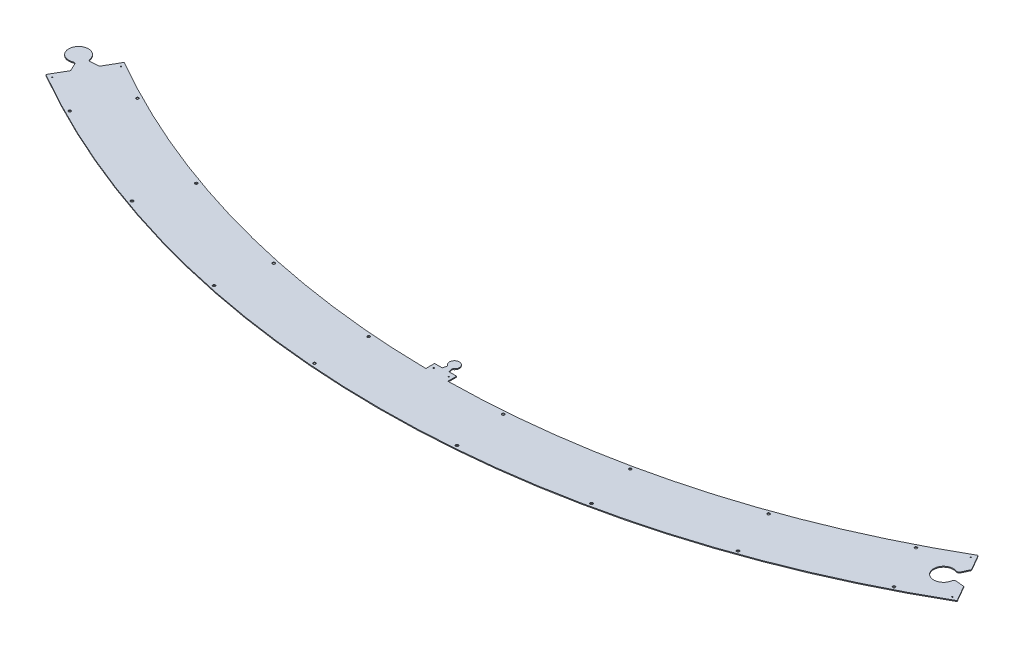
SolidWorks part; units mm, degrees
ref_plane "Front Plane" through (0, 0, 0) normal (0, 0, 1) x (1, 0, 0)
ref_plane "Top Plane" through (0, 0, 0) normal (0, 1, 0) x (1, 0, 0)
ref_plane "Right Plane" through (0, 0, 0) normal (1, 0, 0) x (0, 0, -1)
sketch "Sketch1" plane through (0, 0, 0) normal (0, 1, 0) x (1, 0, 0)
  line L0 (0, 0) -> (0, -2065) construction
  line L1 (0, 0) -> (-1032.5, -1788.3425) construction
  line L2 (0, 0) -> (1032.5, -1788.3425) construction
  line L3 (967.5, -1675.7592) -> (1032.5, -1788.3425)
  line L5 (-25, -1934.8385) -> (-25, -1915)
  line L6 (-25, -1915) -> (25, -1915)
  line L7 (25, -1934.8385) -> (25, -1915)
  line L8 (-967.5, -1675.7592) -> (-1032.5, -1788.3425)
  line L9 (0, 0) -> (933.8184, -1832.8208) construction
  line L10 (967.5, -1675.7592) -> (971.7433, -1673.3093) construction
  line L11 (1032.5, -1788.3425) -> (1036.3111, -1786.1421) construction
  arc A0 (-1032.5, -1788.3425) -> (1032.5, -1788.3425) centre (0, 0) ccw
  arc A1 (-967.5, -1675.7592) -> (-25, -1934.8385) centre (0, 0) ccw
  arc A2 (25, -1934.8385) -> (967.5, -1675.7592) centre (0, 0) ccw
  arc A3 (-967.5, -1675.7592) -> (967.5, -1675.7592) centre (0, 0) ccw construction
  circle A4 centre (-17, -1925) radius 1.25
  circle A5 centre (17, -1925) radius 1.25
  arc A7 (25.1034, -1942.8378) -> (971.5, -1682.6874) centre (0, 0) ccw construction
  circle A8 centre (962.8397, -1687.6874) radius 1.25
  arc A9 (-1028.5, -1781.4143) -> (1028.5, -1781.4143) centre (0, 0) ccw construction
  circle A10 centre (1019.8397, -1786.4143) radius 1.25
  circle A21 centre (686.5983, -1939.0286) radius 3
  circle A22 centre (933.8184, -1832.8208) radius 3
  circle A32 centre (427.6303, -2012.059) radius 3
  circle A33 centre (-1019.8397, -1786.4143) radius 1.25
  circle A34 centre (-962.8397, -1687.6874) radius 1.25
  circle A35 centre (161.3455, -2050.6625) radius 3
  circle A37 centre (-107.7, -2054.1786) radius 3 [skipped]
  circle A38 centre (882.0657, -1731.245) radius 3
  circle A39 centre (648.5467, -1831.5666) radius 3
  circle A40 centre (403.9308, -1900.5496) radius 3
  circle A41 centre (152.4036, -1937.0137) radius 3
  circle A43 centre (-101.7312, -1940.335) radius 3 [skipped]
  circle A44 centre (-152.4036, -1937.0137) radius 3
  circle A45 centre (-403.9308, -1900.5496) radius 3
  circle A46 centre (-648.5467, -1831.5666) radius 3
  circle A47 centre (-882.0657, -1731.245) radius 3
  circle A48 centre (-161.3455, -2050.6625) radius 3
  circle A49 centre (-427.6303, -2012.059) radius 3
  circle A50 centre (-933.8184, -1832.8208) radius 3
  circle A51 centre (-686.5983, -1939.0286) radius 3
  point P5 (0, -1915)
  point P41 (0, 0)
  point P50 (0, 0)
  point P53 (0, 0)
  point P71 (0, 0)
  dimension "D2" = 2065
  dimension "D4" = 2.5
  dimension "D9" = 8
  dimension "D10" = 6
  dimension "D12" = 8
  dimension "D13" = 10
  dimension "D14" = 5
  dimension "D15" = 5
  dimension "D16" = 107.7
  dimension "D19" = 2.5
  dimension "D1" = 30
  dimension "D3" = 50
  dimension "D5" = 150
  dimension "D7" = 10
  dimension "D8" = 8
  dimension "D11" = 10
  dimension "D17" = 8
  dimension "D18" = 8
  dimension "D6" = 130
extrude "Boss-Extrude2" add sketch "Sketch1" along normal blind 2
ref_axis "Axis1" through (0, 2.1, 0) along (0, -1, 0)
sketch "Sketch2" plane through (0, 2, 0) normal (0, 1, 0) x (1, 0, 0)
  line L0 (1000, -1732.0508) -> (965.359, -1752.0508) construction
  line L7 (992.8475, -1751.1632) -> (1012.0021, -1752.839)
  line L8 (1032.5, -1788.3425) -> (967.5, -1675.7592) construction
  line L10 (987.6795, -1750.7111) -> (977.6795, -1733.3906) construction
  line L11 (979.8719, -1728.6888) -> (987.9979, -1711.2626)
  line L13 (987.9979, -1711.2626) -> (1012.0021, -1752.839)
  arc A1 (973.5164, -1731.2312) -> (987.468, -1755.3961) centre (965.359, -1752.0508) ccw
  arc A2 (973.5164, -1731.2312) -> (979.8719, -1728.6888) centre (975.3404, -1726.5758) ccw
  arc A3 (992.8475, -1751.1632) -> (987.468, -1755.3961) centre (992.4117, -1756.1442) ccw
  point P9 (982.6795, -1742.0508)
  dimension "D4" = 20
  dimension "D5" = 5
  dimension "D1" = 10
  dimension "D2" = 40
  dimension "D3" = 35
sketch "Sketch4" plane through (0, 2, 0) normal (0, 1, 0) x (1, 0, 0)
  line L0 (-1000, -1732.0508) -> (-1034.641, -1712.0508) construction
  line L1 (-967.5, -1675.7592) -> (-1032.5, -1788.3425) construction
  line L2 (-1022.3205, -1730.7111) -> (-1012.3205, -1713.3906) construction
  line L3 (-1007.1525, -1712.9384) -> (-987.9979, -1711.2626)
  line L4 (-1020.1281, -1735.4128) -> (-1012.0021, -1752.839)
  line L5 (-987.9979, -1711.2626) -> (-1012.0021, -1752.839)
  line L6 (0, -1915) -> (0, -1895) construction
  line L7 (25, -1915) -> (-25, -1915) construction
  line L8 (0, -1905) -> (5, -1905) construction
  line L9 (5.4863, -1906.815) -> (7.6795, -1915)
  line L10 (-5.4863, -1906.815) -> (-7.6795, -1915)
  line L11 (-7.6795, -1915) -> (7.6795, -1915)
  arc A0 (-1012.532, -1708.7055) -> (-1026.4836, -1732.8704) centre (-1034.641, -1712.0508) ccw
  arc A1 (-1020.1281, -1735.4128) -> (-1026.4836, -1732.8704) centre (-1024.6596, -1737.5259) ccw
  arc A2 (-1007.1525, -1712.9384) -> (-1012.532, -1708.7055) centre (-1007.5883, -1707.9574) cw
  arc A3 (6.4573, -1904.1271) -> (-6.4573, -1904.1271) centre (0, -1895) ccw
  arc A4 (6.4573, -1904.1271) -> (5.4863, -1906.815) centre (7.9011, -1906.168) ccw
  arc A5 (-5.4863, -1906.815) -> (-6.4573, -1904.1271) centre (-7.9011, -1906.168) ccw
  point P7 (-1017.3205, -1722.0508)
  point P30 (-5, -1905)
  dimension "D5" = 5
  dimension "D10" = 2.5
  dimension "D1" = 40
  dimension "D2" = 20
  dimension "D3" = 20
  dimension "D4" = 35
  dimension "D6" = 20
  dimension "D7" = 5
  dimension "D8" = 10
  dimension "D9" = 15
extrude "Cut-Extrude2" cut sketch "Sketch2" against normal up to surface (2 mm away) up to face at (0, 0, 1878.1906)
extrude "Boss-Extrude3" add sketch "Sketch4" against normal up to surface (2 mm away) up to face at (421.3479, 0, 1819.7297)
fillet "Fillet1" radius 1 6 edges at (-1032.5, 1, 1788.3425) (-967.5, 1, 1675.7592) (1032.5, 1, 1788.3425) (967.5, 1, 1675.7592) (-25, 1, 1915) (25, 1, 1915)
